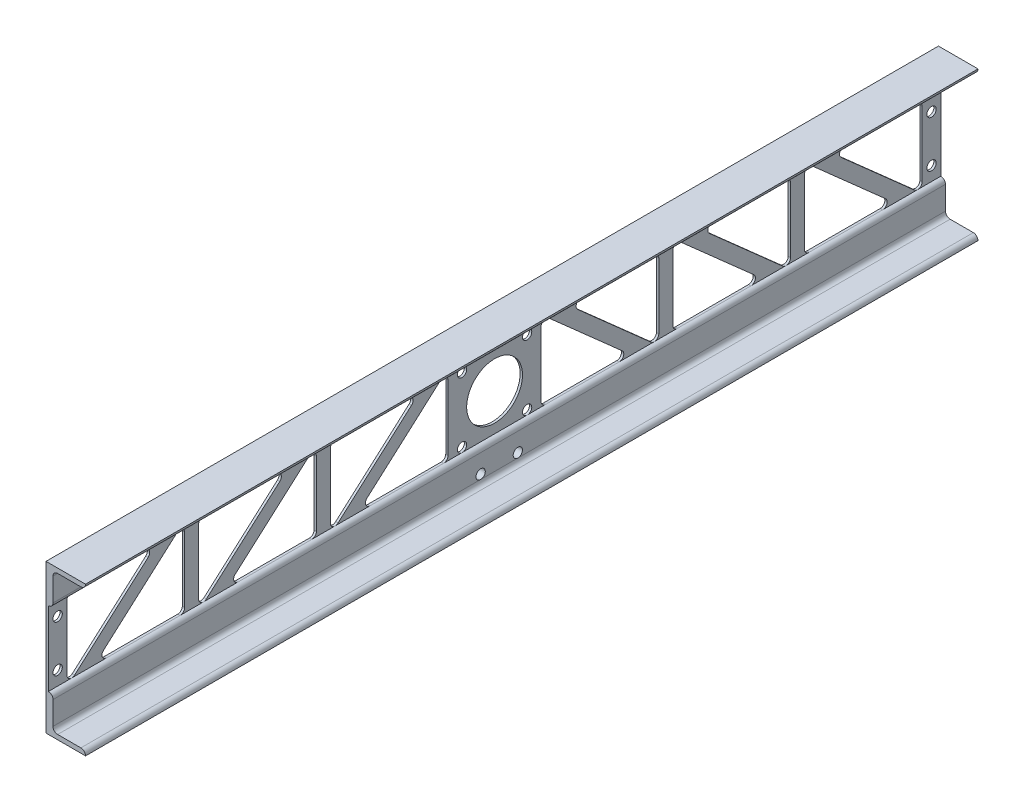
SolidWorks part; units mm, degrees
material "6061 Alloy"
ref_plane "Front Plane" through (0, 0, 0) normal (0, 0, 1) x (1, 0, 0)
ref_plane "Top Plane" through (0, 0, 0) normal (0, 1, 0) x (1, 0, 0)
ref_plane "Right Plane" through (0, 0, 0) normal (1, 0, 0) x (0, 0, -1)
sketch "Sketch1" plane through (0, 0, 0) normal (0, 0, 1) x (1, 0, 0)
  line L1 (0, 0) -> (1.6002, 0)
  line L2 (0, 0) -> (0, 101.6)
  line L3 (0, 101.6) -> (1.6002, 101.6)
  line L4 (1.6002, 0) -> (1.6002, 101.6)
  dimension "D1" = 101.6
  dimension "D2" = 1.6002
extrude "Boss-Extrude1" add sketch "Sketch1" along normal mid plane 609.6
sketch "Sketch2" plane through (0, 0, 0) normal (0, 0, 1) x (1, 0, 0)
  line L0 (27.0002, 101.6) -> (1.6002, 101.6)
  line L1 (1.6002, 101.6) -> (1.6002, 76.2)
  line L2 (4.7752, 79.375) -> (4.7752, 95.25)
  line L3 (7.9502, 98.425) -> (23.8252, 98.425)
  line L4 (1.6002, 50.8) -> (27.0002, 50.8) construction
  line L5 (1.6002, 0) -> (1.6002, 101.6) construction
  line L6 (7.9502, 3.175) -> (23.8252, 3.175)
  line L7 (4.7752, 22.225) -> (4.7752, 6.35)
  line L8 (1.6002, 0) -> (1.6002, 25.4)
  line L9 (27.0002, 0) -> (1.6002, 0)
  arc A0 (1.6002, 76.2) -> (4.7752, 79.375) centre (1.6002, 79.375) ccw
  arc A1 (27.0002, 101.6) -> (23.8252, 98.425) centre (23.8252, 101.6) cw
  arc A2 (4.7752, 95.25) -> (7.9502, 98.425) centre (7.9502, 95.25) cw
  arc A3 (4.7752, 6.35) -> (7.9502, 3.175) centre (7.9502, 6.35) ccw
  arc A4 (27.0002, 0) -> (23.8252, 3.175) centre (23.8252, 0) ccw
  arc A5 (1.6002, 25.4) -> (4.7752, 22.225) centre (1.6002, 22.225) cw
  dimension "D1" = 3.175
  dimension "D2" = 25.4
extrude "Boss-Extrude2" add sketch "Sketch2" along normal mid plane 609.6
sketch "Sketch3" plane through (1.6002, 0, 0) normal (1, 0, 0) x (0, 0, -1)
  line L0 (0, 25.4) -> (0, 76.2) construction
  line L1 (-304.8, 25.4) -> (304.8, 25.4) construction
  line L2 (-304.8, 76.2) -> (304.8, 76.2) construction
  line L3 (-292.1, 73.025) -> (-292.1, 28.575)
  line L4 (-288.925, 76.2) -> (-238.7751, 76.2)
  line L5 (-236.6691, 70.649) -> (-286.819, 26.199)
  line L6 (-304.8, 25.4) -> (-304.8, 76.2) construction
  line L7 (-264.9916, 25.4) -> (-214.8417, 25.4)
  line L8 (-211.6667, 28.575) -> (-211.6667, 73.025)
  line L9 (-216.9476, 75.401) -> (-267.0976, 30.951)
  line L10 (-261.7441, 48.424) -> (-255.4261, 41.2959) construction
  line L11 (-211.6667, 50.8) -> (-202.1417, 50.8) construction
  line L12 (-202.1417, 73.025) -> (-202.1417, 28.575)
  line L13 (-198.9667, 76.2) -> (-148.8167, 76.2)
  line L14 (-146.7108, 70.649) -> (-196.8607, 26.199)
  line L15 (-126.9893, 75.401) -> (-177.1392, 30.951)
  line L16 (-121.7083, 28.575) -> (-121.7083, 73.025)
  line L17 (-175.0333, 25.4) -> (-124.8833, 25.4)
  line L18 (-171.7857, 48.424) -> (-165.4678, 41.2959) construction
  line L19 (-121.7083, 50.8) -> (-112.1833, 50.8) construction
  line L20 (-112.1833, 73.025) -> (-112.1833, 28.575)
  line L21 (-109.0083, 76.2) -> (-58.8584, 76.2)
  line L22 (-56.7524, 70.649) -> (-106.9024, 26.199)
  line L23 (-37.031, 75.401) -> (-87.1809, 30.951)
  line L24 (-31.75, 28.575) -> (-31.75, 73.025)
  line L25 (-85.0749, 25.4) -> (-34.925, 25.4)
  line L26 (-81.8274, 48.424) -> (-75.5095, 41.2959) construction
  line L27 (0, 50.8) -> (-31.75, 50.8) construction
  line L28 (-31.75, 50.8) -> (-22.225, 50.8) construction
  line L29 (81.8274, 48.424) -> (75.5095, 41.2959) construction
  line L30 (121.7083, 50.8) -> (112.1833, 50.8) construction
  line L31 (171.7857, 48.424) -> (165.4678, 41.2959) construction
  line L32 (211.6667, 50.8) -> (202.1417, 50.8) construction
  line L33 (261.7441, 48.424) -> (255.4261, 41.2959) construction
  line L34 (85.0749, 25.4) -> (34.925, 25.4)
  line L35 (31.75, 28.575) -> (31.75, 73.025)
  line L36 (37.031, 75.401) -> (87.1809, 30.951)
  line L37 (56.7524, 70.649) -> (106.9024, 26.199)
  line L38 (109.0083, 76.2) -> (58.8584, 76.2)
  line L39 (112.1833, 73.025) -> (112.1833, 28.575)
  line L40 (175.0333, 25.4) -> (124.8833, 25.4)
  line L41 (121.7083, 28.575) -> (121.7083, 73.025)
  line L42 (126.9893, 75.401) -> (177.1392, 30.951)
  line L43 (146.7108, 70.649) -> (196.8607, 26.199)
  line L44 (198.9667, 76.2) -> (148.8167, 76.2)
  line L45 (202.1417, 73.025) -> (202.1417, 28.575)
  line L46 (216.9476, 75.401) -> (267.0976, 30.951)
  line L47 (211.6667, 28.575) -> (211.6667, 73.025)
  line L48 (264.9916, 25.4) -> (214.8417, 25.4)
  line L49 (236.6691, 70.649) -> (286.819, 26.199)
  line L50 (288.925, 76.2) -> (238.7751, 76.2)
  line L51 (292.1, 73.025) -> (292.1, 28.575)
  circle A0 centre (0, 50.8) radius 19.05
  arc A1 (-292.1, 28.575) -> (-286.819, 26.199) centre (-288.925, 28.575) ccw
  arc A2 (-238.7751, 76.2) -> (-236.6691, 70.649) centre (-238.7751, 73.025) cw
  arc A3 (-292.1, 73.025) -> (-288.925, 76.2) centre (-288.925, 73.025) cw
  arc A4 (-264.9916, 25.4) -> (-267.0976, 30.951) centre (-264.9916, 28.575) cw
  arc A5 (-214.8417, 25.4) -> (-211.6667, 28.575) centre (-214.8417, 28.575) ccw
  arc A6 (-211.6667, 73.025) -> (-216.9476, 75.401) centre (-214.8417, 73.025) ccw
  arc A7 (-202.1417, 73.025) -> (-198.9667, 76.2) centre (-198.9667, 73.025) cw
  arc A8 (-148.8167, 76.2) -> (-146.7108, 70.649) centre (-148.8167, 73.025) cw
  arc A9 (-202.1417, 28.575) -> (-196.8607, 26.199) centre (-198.9667, 28.575) ccw
  arc A10 (-175.0333, 25.4) -> (-177.1392, 30.951) centre (-175.0333, 28.575) cw
  arc A11 (-121.7083, 73.025) -> (-126.9893, 75.401) centre (-124.8833, 73.025) ccw
  arc A12 (-124.8833, 25.4) -> (-121.7083, 28.575) centre (-124.8833, 28.575) ccw
  arc A13 (-112.1833, 73.025) -> (-109.0083, 76.2) centre (-109.0083, 73.025) cw
  arc A14 (-58.8584, 76.2) -> (-56.7524, 70.649) centre (-58.8584, 73.025) cw
  arc A15 (-112.1833, 28.575) -> (-106.9024, 26.199) centre (-109.0083, 28.575) ccw
  arc A16 (-85.0749, 25.4) -> (-87.1809, 30.951) centre (-85.0749, 28.575) cw
  arc A17 (-31.75, 73.025) -> (-37.031, 75.401) centre (-34.925, 73.025) ccw
  arc A18 (-34.925, 25.4) -> (-31.75, 28.575) centre (-34.925, 28.575) ccw
  arc A19 (34.925, 25.4) -> (31.75, 28.575) centre (34.925, 28.575) cw
  arc A20 (31.75, 73.025) -> (37.031, 75.401) centre (34.925, 73.025) cw
  arc A21 (85.0749, 25.4) -> (87.1809, 30.951) centre (85.0749, 28.575) ccw
  arc A22 (112.1833, 28.575) -> (106.9024, 26.199) centre (109.0083, 28.575) cw
  arc A23 (58.8584, 76.2) -> (56.7524, 70.649) centre (58.8584, 73.025) ccw
  arc A24 (112.1833, 73.025) -> (109.0083, 76.2) centre (109.0083, 73.025) ccw
  arc A25 (124.8833, 25.4) -> (121.7083, 28.575) centre (124.8833, 28.575) cw
  arc A26 (121.7083, 73.025) -> (126.9893, 75.401) centre (124.8833, 73.025) cw
  arc A27 (175.0333, 25.4) -> (177.1392, 30.951) centre (175.0333, 28.575) ccw
  arc A28 (202.1417, 28.575) -> (196.8607, 26.199) centre (198.9667, 28.575) cw
  arc A29 (148.8167, 76.2) -> (146.7108, 70.649) centre (148.8167, 73.025) ccw
  arc A30 (202.1417, 73.025) -> (198.9667, 76.2) centre (198.9667, 73.025) ccw
  arc A31 (211.6667, 73.025) -> (216.9476, 75.401) centre (214.8417, 73.025) cw
  arc A32 (214.8417, 25.4) -> (211.6667, 28.575) centre (214.8417, 28.575) cw
  arc A33 (264.9916, 25.4) -> (267.0976, 30.951) centre (264.9916, 28.575) ccw
  arc A34 (292.1, 73.025) -> (288.925, 76.2) centre (288.925, 73.025) ccw
  arc A35 (238.7751, 76.2) -> (236.6691, 70.649) centre (238.7751, 73.025) ccw
  arc A36 (292.1, 28.575) -> (286.819, 26.199) centre (288.925, 28.575) cw
  point P16 (-230.4063, 76.2)
  point P19 (-292.1, 76.2)
  point P20 (-288.925, 25.4)
  point P28 (-273.3604, 25.4)
  point P31 (-211.6667, 25.4)
  point P34 (-214.8417, 76.2)
  point P148 (214.8417, 76.2)
  point P149 (211.6667, 25.4)
  point P150 (273.3604, 25.4)
  point P151 (288.925, 25.4)
  point P152 (292.1, 76.2)
  point P153 (230.4063, 76.2)
  dimension "D1" = 38.1
  dimension "D2" = 3.175
  dimension "D4" = 3.175
  dimension "D3" = 12.7
  dimension "D6" = 9.525
  dimension "D7" = 31.75
  dimension "D5" = 3
extrude "Cut-Extrude1" cut sketch "Sketch3" against normal through all
sketch "Sketch4" plane through (1.6002, 0, 0) normal (1, 0, 0) x (0, 0, -1)
  line L1 (-22.225, 28.575) -> (22.225, 28.575) construction
  line L2 (-22.225, 28.575) -> (-22.225, 73.025) construction
  line L3 (-22.225, 73.025) -> (22.225, 73.025) construction
  line L4 (22.225, 28.575) -> (22.225, 73.025) construction
  line L5 (-22.225, 28.575) -> (22.225, 73.025) construction
  line L6 (-22.225, 73.025) -> (22.225, 28.575) construction
  circle A0 centre (-22.225, 73.025) radius 3.175
  circle A1 centre (22.225, 73.025) radius 3.175
  circle A2 centre (22.225, 28.575) radius 3.175
  circle A3 centre (-22.225, 28.575) radius 3.175
  point P0 (0, 50.8)
  dimension "D2" = 6.35
  dimension "D1" = 44.45
extrude "Cut-Extrude2" cut sketch "Sketch4" against normal through all
sketch "Sketch5" plane through (1.6002, 0, 0) normal (1, 0, 0) x (0, 0, -1)
  line L0 (-304.8, 50.8) -> (-292.1, 50.8) construction
  line L1 (-304.8, 25.4) -> (-304.8, 76.2) construction
  line L2 (-292.1, 73.025) -> (-292.1, 28.575) construction
  line L3 (-298.45, 66.675) -> (-298.45, 34.925) construction
  line L4 (0, 76.2) -> (0, 25.4) construction
  line L5 (-22.225, 76.2) -> (22.225, 76.2) construction
  line L6 (-22.225, 25.4) -> (22.225, 25.4) construction
  line L7 (298.45, 66.675) -> (298.45, 34.925) construction
  line L8 (304.8, 50.8) -> (292.1, 50.8) construction
  circle A0 centre (-298.45, 66.675) radius 3.175
  circle A1 centre (-298.45, 34.925) radius 3.175
  circle A2 centre (298.45, 34.925) radius 3.175
  circle A3 centre (298.45, 66.675) radius 3.175
  point P8 (-298.45, 50.8)
  point P23 (298.45, 50.8)
  dimension "D2" = 6.35
  dimension "D1" = 31.75
extrude "Cut-Extrude3" cut sketch "Sketch5" against normal through all
sketch "Sketch6" plane through (4.7752, 0, 0) normal (1, 0, 0) x (0, 0, -1)
  line L0 (114.3, 92.075) -> (139.7, 92.075) construction
  line L1 (0, 50.8) -> (127, 50.8) construction
  line L2 (127, 50.8) -> (127, 98.425) construction
  line L4 (-304.8, 98.425) -> (304.8, 98.425) construction
  circle A0 centre (139.7, 92.075) radius 3.175
  circle A1 centre (114.3, 92.075) radius 3.175
  point P7 (127, 92.075)
  dimension "D1" = 6.35
  dimension "D2" = 25.4
  dimension "D3" = 127
  dimension "D4" = 6.35
extrude "Cut-Extrude4" cut sketch "Sketch6" against normal through all
sketch "Sketch7" plane through (4.7752, 0, 0) normal (1, 0, 0) x (0, 0, -1)
  line L0 (-190.5, 92.075) -> (-165.1, 92.075) construction
  line L1 (-177.8, 98.425) -> (-177.8, 85.725) construction
  line L2 (-304.8, 98.425) -> (304.8, 98.425) construction
  line L4 (-304.8, 79.375) -> (-304.8, 95.25) construction
  circle A0 centre (-165.1, 92.075) radius 3.175
  circle A1 centre (-190.5, 92.075) radius 3.175
  point P6 (-177.8, 92.075)
  dimension "D1" = 6.35
  dimension "D2" = 25.4
  dimension "D3" = 12.7
  dimension "D4" = 127
extrude "Cut-Extrude5" cut sketch "Sketch7" against normal through all
sketch "Sketch8" plane through (4.7752, 0, 0) normal (1, 0, 0) x (0, 0, -1)
  line L0 (0, 15.875) -> (0, 3.175) construction
  line L1 (-304.8, 3.175) -> (304.8, 3.175) construction
  line L2 (-12.7, 9.525) -> (12.7, 9.525) construction
  circle A0 centre (-12.7, 9.525) radius 3.175
  circle A1 centre (12.7, 9.525) radius 3.175
  point P7 (0, 9.525)
  dimension "D3" = 6.35
  dimension "D1" = 12.7
  dimension "D2" = 25.4
extrude "Cut-Extrude6" cut sketch "Sketch8" against normal through all
